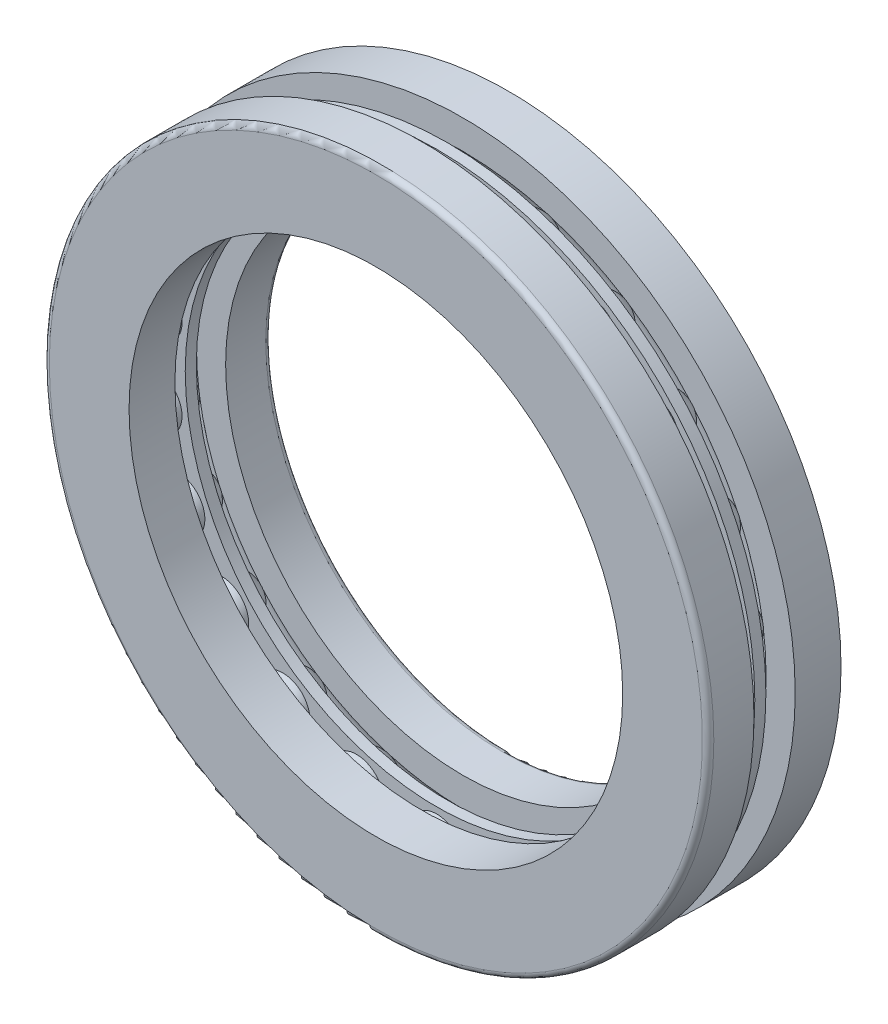
SolidWorks part; units mm, degrees
ref_plane "Front Plane" through (0, 0, 0) normal (0, 0, 1) x (1, 0, 0)
ref_plane "Top Plane" through (0, 0, 0) normal (0, 1, 0) x (1, 0, 0)
ref_plane "Right Plane" through (0, 0, 0) normal (1, 0, 0) x (0, 0, -1)
sketch "BaseSke" plane through (0, 0, 0) normal (1, 0, 0) x (0, 0, -1)
  line L0 (-22.7078, 0) -> (24.6132, 0) construction
  line L1 (-22.7078, 30) -> (24.6132, 30) construction
  line L2 (0, 129.5214) -> (0, -86.3012) construction
  line L3 (0, 32.9167) -> (0, 27.0833)
  line L6 (-7, 35) -> (-7, 26) construction
  line L8 (7, 35) -> (7, 25) construction
  arc A0 (0, 32.9167) -> (0, 27.0833) centre (0, 30) ccw
  dimension "Ball_diameter" = 5.8333
  dimension "D1" = 30
  dimension "D2" = 7
  dimension "Bearing_Thickness" = 14
revolve "Ball" add sketch "BaseSke" angle 360 about L3
sketch "InnerRaceSke" plane through (0, 0, 0) normal (1, 0, 0) x (0, 0, -1)
  line L0 (2.1724, 28.0689) -> (2.1724, 25)
  line L1 (2.1724, 35) -> (7, 35)
  line L2 (2.1724, 35) -> (2.1724, 31.9311)
  line L3 (2.1724, 25) -> (7, 25)
  line L4 (7, 35) -> (7, 25)
  line L5 (-18.959, 0) -> (19.5136, 0) construction
  arc A0 (2.1724, 28.0689) -> (2.1724, 31.9311) centre (0, 30) ccw
  arc A2 (0, 32.9167) -> (0, 27.0833) centre (0, 30) ccw construction
  dimension "D1" = 5.8133
  dimension "D2" = 4.8276
revolve "InnerRace" add sketch "InnerRaceSke" angle 360 about L5
sketch "OuterRaceSke" plane through (0, 0, 0) normal (1, 0, 0) x (0, 0, -1)
  line L0 (-2.1724, 28.0689) -> (-2.1724, 26)
  line L1 (-7, 35) -> (-2.1724, 35)
  line L2 (-7, 35) -> (-7, 26)
  line L3 (-7, 26) -> (-2.1724, 26)
  line L4 (-2.1724, 35) -> (-2.1724, 31.9311)
  line L5 (-27.1643, 0) -> (37.3715, 0) construction
  arc A0 (-2.1724, 31.9311) -> (-2.1724, 28.0689) centre (0, 30) ccw
  arc A1 (0, 32.9167) -> (0, 27.0833) centre (0, 30) ccw construction
  dimension "D1" = 5.8133
  dimension "D2" = 4.8276
revolve "OuterRace" add sketch "OuterRaceSke" angle 360 about L5
fillet "Fillet1" radius 0.6 2 edges at (35, 0, 7) (25, 0, -7)
pattern_circular "CirPatternBall" count 22 over 360 about axis through (0, 0, 27.1643) along (0, 0, -1) of "Ball"
sketch "CageSke" plane through (0, 0, 0) normal (1, 0, 0) x (0, 0, -1)
  line L0 (0, 59.1614) -> (0, 0) construction
  line L1 (0.5833, 33.5) -> (-0.5833, 33.5)
  line L2 (0.5833, 33.5) -> (0.5833, 26.5)
  line L3 (0.5833, 26.5) -> (-0.5833, 26.5)
  line L4 (-0.5833, 33.5) -> (-0.5833, 26.5)
  line L5 (-23.077, 0) -> (28.998, 0) construction
  circle A0 centre (0, 30) radius 3.5483 construction
  arc A1 (0, 32.9167) -> (0, 27.0833) centre (0, 30) ccw construction
  dimension "D1" = 1.1667
  dimension "D2" = 7
revolve "Cage" add sketch "CageSke" angle 360 about L5
sketch "SimplifiedSke" plane through (0, 0, 0) normal (1, 0, 0) x (0, 0, -1)
  line L0 (-32.3536, 0) -> (41.9236, 0) construction
  circle A0 centre (0, 30) radius 2.9167
  arc A1 (0, 32.9167) -> (0, 27.0833) centre (0, 30) ccw construction
revolve "Simplified" [suppressed] add sketch "SimplifiedSke" angle 360 about L0
equation "\"D2@BaseSke\" = \"Bearing_Thickness@BaseSke\"/2"
equation "\"D1@BaseSke\" =  ( \"Diameter2@BaseSke\" + \"Bearing_Inside_Diameter@BaseSke\" )  / 4"
equation "\"Ball_diameter@BaseSke\" = \"Bearing_Thickness@BaseSke\"  / 2.4"
equation "\"D1@InnerRaceSke\" = \"Ball_diameter@BaseSke\"-0.02"
equation "\"D2@InnerRaceSke\" = \"Bearing_Thickness@BaseSke\"/2.9"
equation "\"D1@OuterRaceSke\" = \"Ball_diameter@BaseSke\"-0.02"
equation "\"D2@OuterRaceSke\" = \"Bearing_Thickness@BaseSke\" / 2.9"
equation "\"D1@CirPatternBall\" =  pi  * \"D1@BaseSke\" * 2 / \"Ball_diameter@BaseSke\"/1.5"
equation "\"D1@CageSke\" = \"Ball_diameter@BaseSke\"/5"
equation "\"D2@CageSke\" = \"Ball_diameter@BaseSke\" * 1.2"
